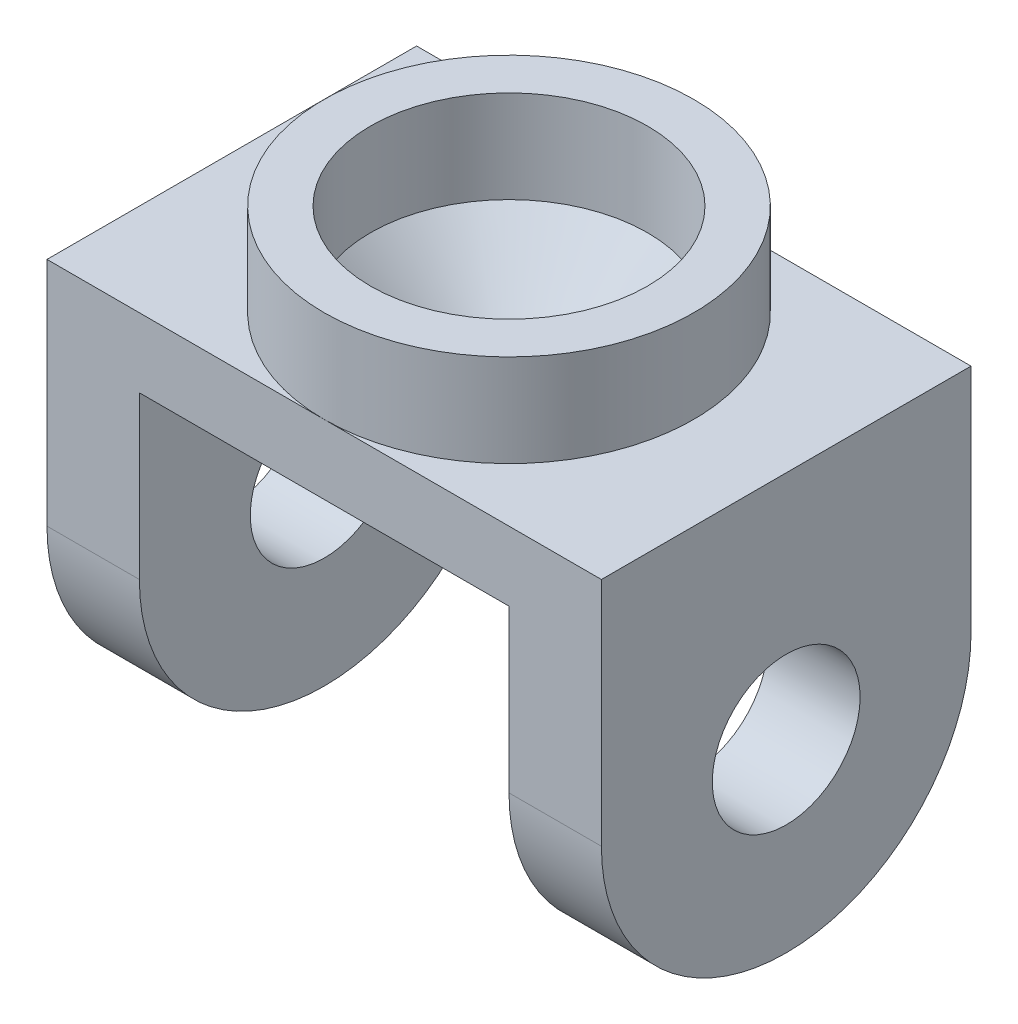
SolidWorks part; units mm, degrees
ref_plane "Front Plane" through (0, 0, 0) normal (0, 0, 1) x (1, 0, 0)
ref_plane "Top Plane" through (0, 0, 0) normal (0, 1, 0) x (1, 0, 0)
ref_plane "Right Plane" through (0, 0, 0) normal (1, 0, 0) x (0, 0, -1)
sketch "Sketch1" plane through (0, 0, 0) normal (0, 1, 0) x (1, 0, 0)
  line L1 (-152.4, -101.6) -> (152.4, -101.6)
  line L2 (-152.4, -101.6) -> (-152.4, 101.6)
  line L3 (-152.4, 101.6) -> (152.4, 101.6)
  line L4 (152.4, -101.6) -> (152.4, 101.6)
  line L5 (-152.4, -101.6) -> (152.4, 101.6) construction
  line L6 (-152.4, 101.6) -> (152.4, -101.6) construction
  point P0 (0, 0)
  dimension "D1" = 304.8
  dimension "D2" = 203.2
extrude "Boss-Extrude1" add sketch "Sketch1" along normal blind 228.6
sketch "Sketch2" plane through (0, 228.6, 0) normal (0, 1, 0) x (1, 0, 0)
  circle A0 centre (0, 0) radius 101.6
  circle A1 centre (0, 0) radius 76.2
  dimension "D1" = 203.2
  dimension "D2" = 25.4
extrude "Boss-Extrude2" add sketch "Sketch2" along normal blind 50.8
sketch "Sketch3" plane through (0, 228.6, 0) normal (0, 1, 0) x (1, 0, 0)
  circle A0 centre (0, 0) radius 38.1
  dimension "D1" = 76.2
extrude "Cut-Extrude1" cut sketch "Sketch3" against normal blind 38.1
sketch "Sketch4" plane through (0, 0, 0) normal (0, -1, 0) x (1, 0, 0)
  line L0 (-152.4, 101.6) -> (152.4, 101.6) construction
  line L1 (-101.6, -101.6) -> (101.6, -101.6)
  line L2 (-101.6, -101.6) -> (-101.6, 101.6)
  line L3 (-101.6, 101.6) -> (101.6, 101.6)
  line L4 (101.6, -101.6) -> (101.6, 101.6)
  line L5 (-101.6, -101.6) -> (101.6, 101.6) construction
  line L6 (-101.6, 101.6) -> (101.6, -101.6) construction
  point P0 (0, 0)
  dimension "D1" = 203.2
extrude "Cut-Extrude2" cut sketch "Sketch4" against normal blind 190.5
sketch "Sketch5" plane through (152.4, 0, 0) normal (1, 0, 0) x (0, 0, -1)
  line L0 (0, 228.6) -> (0, 101.6) construction
  line L1 (101.6, 228.6) -> (-101.6, 228.6) construction
  circle A0 centre (0, 101.6) radius 40.64
  dimension "D2" = 81.28
  dimension "D1" = 127
extrude "Cut-Extrude3" cut sketch "Sketch5" against normal blind 304.8
fillet "Fillet1" radius 101.6 4 edges at (127, 0, -101.6) (127, 0, 101.6) (-127, 0, -101.6) (-127, 0, 101.6)
chamfer "Chamfer1" distance 38.1 1 edges at (0, 228.6, 38.1)
